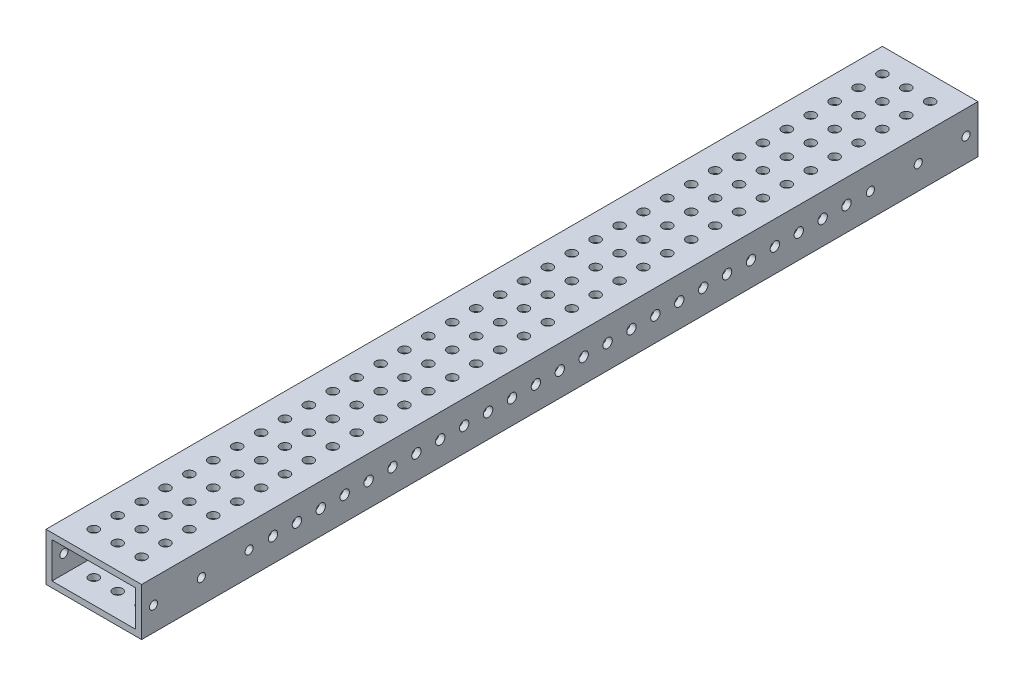
SolidWorks part; units mm, degrees
material "6061-T6 (SS)"
ref_plane "Front Plane" through (0, 0, 0) normal (0, 0, 1) x (1, 0, 0)
ref_plane "Top Plane" through (0, 0, 0) normal (0, 1, 0) x (1, 0, 0)
ref_plane "Right Plane" through (0, 0, 0) normal (1, 0, 0) x (0, 0, -1)
sketch "Sketch1" plane through (0, 0, 0) normal (0, 0, 1) x (1, 0, 0)
  line L0 (-22.225, 9.525) -> (22.225, 9.525)
  line L1 (-25.4, 12.7) -> (25.4, 12.7)
  line L2 (-25.4, 12.7) -> (-25.4, -12.7)
  line L3 (-25.4, -12.7) -> (25.4, -12.7)
  line L4 (25.4, 12.7) -> (25.4, -12.7)
  line L5 (22.225, 9.525) -> (22.225, -9.525)
  line L6 (-22.225, -9.525) -> (22.225, -9.525)
  line L7 (-22.225, 9.525) -> (-22.225, -9.525)
  line L8 (-25.4, 12.7) -> (25.4, -12.7) construction
  line L9 (25.4, 12.7) -> (-25.4, -12.7) construction
  point P5 (0, 0)
  dimension "D1" = 50.8
  dimension "D2" = 25.4
  dimension "D3" = 3.175
extrude "Boss-Extrude1" add sketch "Sketch1" along normal mid plane 444.5
sketch "Sketch2" plane through (0, 12.7, 0) normal (0, 1, 0) x (1, 0, 0)
  line L0 (25.4, -222.25) -> (-25.4, -222.25) construction
  line L1 (-25.4, -222.25) -> (-25.4, 222.25) construction
  line L2 (-12.7, -209.55) -> (0, -209.55) construction
  line L3 (0, -209.55) -> (12.7, -209.55) construction
  line L4 (25.4, 222.25) -> (-25.4, 222.25) construction
  circle A0 centre (0, -209.55) radius 2.5527
  circle A1 centre (12.7, -209.55) radius 2.5527
  circle A2 centre (-12.7, -209.55) radius 2.5527
  circle A3 centre (-12.7, -196.85) radius 2.5527
  circle A4 centre (0, -196.85) radius 2.5527
  circle A5 centre (12.7, -196.85) radius 2.5527
  circle A6 centre (-12.7, -184.15) radius 2.5527
  circle A7 centre (0, -184.15) radius 2.5527
  circle A8 centre (12.7, -184.15) radius 2.5527
  circle A9 centre (-12.7, -171.45) radius 2.5527
  circle A10 centre (0, -171.45) radius 2.5527
  circle A11 centre (12.7, -171.45) radius 2.5527
  circle A12 centre (-12.7, -158.75) radius 2.5527
  circle A13 centre (0, -158.75) radius 2.5527
  circle A14 centre (12.7, -158.75) radius 2.5527
  circle A15 centre (-12.7, -146.05) radius 2.5527
  circle A16 centre (0, -146.05) radius 2.5527
  circle A17 centre (12.7, -146.05) radius 2.5527
  circle A18 centre (-12.7, -133.35) radius 2.5527
  circle A19 centre (0, -133.35) radius 2.5527
  circle A20 centre (12.7, -133.35) radius 2.5527
  circle A21 centre (-12.7, -120.65) radius 2.5527
  circle A22 centre (0, -120.65) radius 2.5527
  circle A23 centre (12.7, -120.65) radius 2.5527
  circle A24 centre (-12.7, -107.95) radius 2.5527
  circle A25 centre (0, -107.95) radius 2.5527
  circle A26 centre (12.7, -107.95) radius 2.5527
  circle A27 centre (-12.7, -95.25) radius 2.5527
  circle A28 centre (0, -95.25) radius 2.5527
  circle A29 centre (12.7, -95.25) radius 2.5527
  circle A30 centre (-12.7, -82.55) radius 2.5527
  circle A31 centre (0, -82.55) radius 2.5527
  circle A32 centre (12.7, -82.55) radius 2.5527
  circle A33 centre (-12.7, -69.85) radius 2.5527
  circle A34 centre (0, -69.85) radius 2.5527
  circle A35 centre (12.7, -69.85) radius 2.5527
  circle A36 centre (-12.7, -57.15) radius 2.5527
  circle A37 centre (0, -57.15) radius 2.5527
  circle A38 centre (12.7, -57.15) radius 2.5527
  circle A39 centre (-12.7, -44.45) radius 2.5527
  circle A40 centre (0, -44.45) radius 2.5527
  circle A41 centre (12.7, -44.45) radius 2.5527
  circle A42 centre (-12.7, -31.75) radius 2.5527
  circle A43 centre (0, -31.75) radius 2.5527
  circle A44 centre (12.7, -31.75) radius 2.5527
  circle A45 centre (-12.7, -19.05) radius 2.5527
  circle A46 centre (0, -19.05) radius 2.5527
  circle A47 centre (12.7, -19.05) radius 2.5527
  circle A48 centre (-12.7, -6.35) radius 2.5527
  circle A49 centre (0, -6.35) radius 2.5527
  circle A50 centre (12.7, -6.35) radius 2.5527
  circle A51 centre (-12.7, 6.35) radius 2.5527
  circle A52 centre (0, 6.35) radius 2.5527
  circle A53 centre (12.7, 6.35) radius 2.5527
  circle A54 centre (-12.7, 19.05) radius 2.5527
  circle A55 centre (0, 19.05) radius 2.5527
  circle A56 centre (12.7, 19.05) radius 2.5527
  circle A57 centre (-12.7, 31.75) radius 2.5527
  circle A58 centre (0, 31.75) radius 2.5527
  circle A59 centre (12.7, 31.75) radius 2.5527
  circle A60 centre (-12.7, 44.45) radius 2.5527
  circle A61 centre (0, 44.45) radius 2.5527
  circle A62 centre (12.7, 44.45) radius 2.5527
  circle A63 centre (-12.7, 57.15) radius 2.5527
  circle A64 centre (0, 57.15) radius 2.5527
  circle A65 centre (12.7, 57.15) radius 2.5527
  circle A66 centre (-12.7, 69.85) radius 2.5527
  circle A67 centre (0, 69.85) radius 2.5527
  circle A68 centre (12.7, 69.85) radius 2.5527
  circle A69 centre (-12.7, 82.55) radius 2.5527
  circle A70 centre (0, 82.55) radius 2.5527
  circle A71 centre (12.7, 82.55) radius 2.5527
  circle A72 centre (-12.7, 95.25) radius 2.5527
  circle A73 centre (0, 95.25) radius 2.5527
  circle A74 centre (12.7, 95.25) radius 2.5527
  circle A75 centre (-12.7, 107.95) radius 2.5527
  circle A76 centre (0, 107.95) radius 2.5527
  circle A77 centre (12.7, 107.95) radius 2.5527
  circle A78 centre (-12.7, 120.65) radius 2.5527
  circle A79 centre (0, 120.65) radius 2.5527
  circle A80 centre (12.7, 120.65) radius 2.5527
  circle A81 centre (-12.7, 133.35) radius 2.5527
  circle A82 centre (0, 133.35) radius 2.5527
  circle A83 centre (12.7, 133.35) radius 2.5527
  circle A84 centre (-12.7, 146.05) radius 2.5527
  circle A85 centre (0, 146.05) radius 2.5527
  circle A86 centre (12.7, 146.05) radius 2.5527
  circle A87 centre (-12.7, 158.75) radius 2.5527
  circle A88 centre (0, 158.75) radius 2.5527
  circle A89 centre (12.7, 158.75) radius 2.5527
  circle A90 centre (-12.7, 171.45) radius 2.5527
  circle A91 centre (0, 171.45) radius 2.5527
  circle A92 centre (12.7, 171.45) radius 2.5527
  circle A93 centre (-12.7, 184.15) radius 2.5527
  circle A94 centre (0, 184.15) radius 2.5527
  circle A95 centre (12.7, 184.15) radius 2.5527
  circle A96 centre (-12.7, 196.85) radius 2.5527
  circle A97 centre (0, 196.85) radius 2.5527
  circle A98 centre (12.7, 196.85) radius 2.5527
  circle A99 centre (-12.7, 209.55) radius 2.5527
  circle A100 centre (0, 209.55) radius 2.5527
  circle A101 centre (12.7, 209.55) radius 2.5527
  circle A108 centre (-12.7, 234.95) radius 2.5527 [skipped]
  circle A109 centre (0, 234.95) radius 2.5527 [skipped]
  circle A110 centre (12.7, 234.95) radius 2.5527 [skipped]
  circle A111 centre (-12.7, 222.25) radius 2.5527 [skipped]
  circle A112 centre (0, 222.25) radius 2.5527 [skipped]
  circle A113 centre (12.7, 222.25) radius 2.5527 [skipped]
  dimension "D2" = 5.1054
  dimension "D4" = 12.7
  dimension "D1" = 12.7
  dimension "D3" = 25.4
  dimension "D6" = 12.7
  dimension "D7" = 12.7
  dimension "D5" = 36
extrude "Cut-Extrude1" cut sketch "Sketch2" against normal through all
sketch "Sketch3" plane through (25.4, 0, 0) normal (1, 0, 0) x (0, 0, -1)
  line L0 (-222.25, -12.7) -> (-222.25, 12.7) construction
  line L1 (-222.25, 12.7) -> (222.25, 12.7) construction
  line L2 (222.25, -12.7) -> (222.25, 12.7) construction
  circle A0 centre (-215.9, 0) radius 2.1527
  circle A1 centre (-190.5, 0) radius 2.1527
  circle A2 centre (-165.1, 0) radius 2.1527
  circle A3 centre (215.9, 0) radius 2.159
  circle A4 centre (190.5, 0) radius 2.159
  circle A5 centre (165.1, 0) radius 2.159
  dimension "D2" = 4.3053
  dimension "D9" = 4.318
  dimension "D1" = 6.35
  dimension "D3" = 12.7
  dimension "D4" = 31.75
  dimension "D5" = 12.7
  dimension "D6" = 57.15
  dimension "D7" = 12.7
  dimension "D8" = 6.35
  dimension "D10" = 12.7
  dimension "D11" = 31.75
  dimension "D12" = 57.15
  dimension "D13" = 12.7
  dimension "D14" = 12.7
extrude "Cut-Extrude2" cut sketch "Sketch3" against normal through all
sketch "Sketch4" plane through (25.4, 0, 0) normal (1, 0, 0) x (0, 0, -1)
  line L1 (-222.25, -12.7) -> (-222.25, 12.7) construction
  line L2 (-222.25, -12.7) -> (222.25, -12.7) construction
  circle A2 centre (-215.9, 0) radius 2.4892 construction
  circle A3 centre (-203.2, 0) radius 2.4892 construction
  circle A16 centre (-190.5, 0) radius 2.4892 construction
  circle A17 centre (-177.8, 0) radius 2.4892 construction
  circle A18 centre (-165.1, 0) radius 2.4892 construction
  circle A35 centre (-152.4, 0) radius 2.4892
  circle A36 centre (-139.7, 0) radius 2.4892
  circle A37 centre (-127, 0) radius 2.4892
  circle A38 centre (-114.3, 0) radius 2.4892
  circle A39 centre (-101.6, 0) radius 2.4892
  circle A40 centre (-88.9, 0) radius 2.4892
  circle A41 centre (-76.2, 0) radius 2.4892
  circle A42 centre (-63.5, 0) radius 2.4892
  circle A43 centre (-50.8, 0) radius 2.4892
  circle A44 centre (-38.1, 0) radius 2.4892
  circle A45 centre (-25.4, 0) radius 2.4892
  circle A46 centre (-12.7, 0) radius 2.4892
  circle A47 centre (0, 0) radius 2.4892
  circle A48 centre (12.7, 0) radius 2.4892
  circle A49 centre (25.4, 0) radius 2.4892
  circle A50 centre (38.1, 0) radius 2.4892
  circle A51 centre (50.8, 0) radius 2.4892
  circle A52 centre (63.5, 0) radius 2.4892
  circle A53 centre (76.2, 0) radius 2.4892
  circle A54 centre (88.9, 0) radius 2.4892
  circle A55 centre (101.6, 0) radius 2.4892
  circle A56 centre (114.3, 0) radius 2.4892
  circle A57 centre (127, 0) radius 2.4892
  circle A58 centre (139.7, 0) radius 2.4892
  circle A59 centre (152.4, 0) radius 2.4892
  circle A60 centre (165.1, 0) radius 2.4892 construction
  circle A61 centre (177.8, 0) radius 2.4892 construction
  circle A62 centre (190.5, 0) radius 2.4892 construction
  circle A63 centre (203.2, 0) radius 2.4892 construction
  dimension "D2" = 4.9784
  dimension "D1" = 6.35
  dimension "D3" = 12.7
  dimension "D4" = 12.7
  dimension "D5" = 34
extrude "Cut-Extrude3" cut sketch "Sketch4" against normal through all
